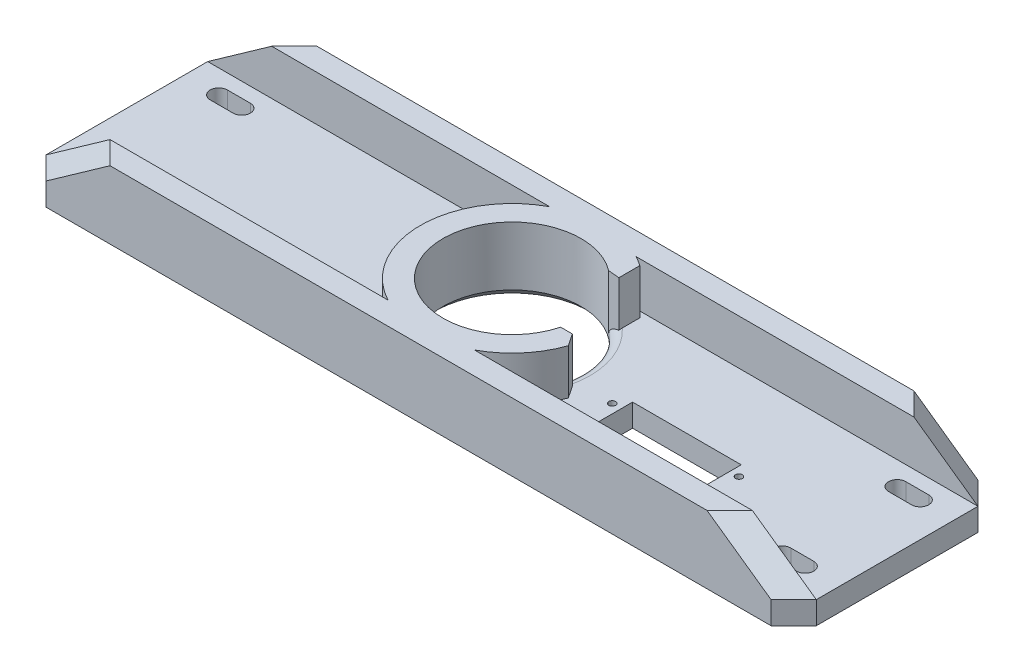
SolidWorks part; units mm, degrees
ref_plane "Front Plane" through (0, 0, 0) normal (0, 0, 1) x (1, 0, 0)
ref_plane "Top Plane" through (0, 0, 0) normal (0, 1, 0) x (1, 0, 0)
ref_plane "Right Plane" through (0, 0, 0) normal (1, 0, 0) x (0, 0, -1)
sketch "Sketch1" plane through (0, 0, 0) normal (0, 1, 0) x (1, 0, 0)
  line L1 (-85.09, 22.86) -> (85.09, 22.86)
  line L2 (-85.09, 22.86) -> (-85.09, -22.86)
  line L3 (-85.09, -22.86) -> (85.09, -22.86)
  line L4 (85.09, 22.86) -> (85.09, -22.86)
  line L5 (-85.09, 22.86) -> (85.09, -22.86) construction
  line L6 (-85.09, -22.86) -> (85.09, 22.86) construction
  point P0 (0, 0)
  dimension "D1" = 170.18
  dimension "D2" = 45.72
extrude "Boss-Extrude1" add sketch "Sketch1" along normal blind 5
sketch "Sketch2" plane through (0, 5, 0) normal (0, 1, 0) x (1, 0, 0)
  line L0 (85.09, 22.86) -> (-85.09, 22.86) construction
  line L1 (85.09, -22.86) -> (85.09, 22.86) construction
  line L2 (-77.4775, 14.6) -> (-72.3975, 14.6)
  line L3 (-77.4775, 10.8) -> (-72.3975, 10.8)
  line L4 (-77.47, -10.8) -> (-72.39, -10.8)
  line L5 (72.39, 14.6) -> (77.47, 14.6)
  line L6 (-72.39, -14.6) -> (-77.47, -14.6)
  line L7 (72.39, -10.8) -> (77.47, -10.8)
  line L8 (77.47, 10.8) -> (72.39, 10.8)
  line L10 (77.47, -14.6) -> (72.39, -14.6)
  arc A0 (-77.4775, 14.6) -> (-77.4775, 10.8) centre (-77.4775, 12.7) ccw
  arc A1 (77.47, 10.8) -> (77.47, 14.6) centre (77.47, 12.7) ccw
  arc A2 (-77.47, -10.8) -> (-77.47, -14.6) centre (-77.47, -12.7) ccw
  arc A3 (77.47, -14.6) -> (77.47, -10.8) centre (77.47, -12.7) ccw
  arc A4 (-72.3975, 10.8) -> (-72.3975, 14.6) centre (-72.3975, 12.7) ccw
  arc A5 (-72.39, -14.6) -> (-72.39, -10.8) centre (-72.39, -12.7) ccw
  arc A6 (72.39, 14.6) -> (72.39, 10.8) centre (72.39, 12.7) ccw
  arc A7 (72.39, -10.8) -> (72.39, -14.6) centre (72.39, -12.7) ccw
  dimension "D2" = 3.8
  dimension "D3" = 3.8
  dimension "D4" = 3.8
  dimension "D5" = 25.4
  dimension "D6" = 25.4
  dimension "D7" = 154.94
  dimension "D8" = 154.9475
  dimension "D9" = 10.16
  dimension "D10" = 10.16
  dimension "D11" = 7.62
  dimension "D12" = 7.62
  dimension "D13" = 3.8
  dimension "D16" = 5.08
  dimension "D17" = 5.08
  dimension "D18" = 5.08
  dimension "D14" = 5.08
extrude "Cut-Extrude1" cut sketch "Sketch2" against normal blind 5
sketch "Sketch4" plane through (0, 5, 0) normal (0, 1, 0) x (1, 0, 0)
  circle A0 centre (0, 0) radius 15.25
  dimension "D1" = 30.5
extrude "Cut-Extrude2" cut sketch "Sketch4" against normal blind 5
sketch "Sketch5" plane through (0, 5, 0) normal (0, 1, 0) x (1, 0, 0)
  line L0 (85.09, -22.86) -> (85.09, 22.86) construction
  line L1 (-85.09, 22.86) -> (85.09, 22.86)
  line L2 (-85.09, 22.86) -> (-85.09, 17.86)
  line L3 (-85.09, 17.86) -> (85.09, 17.86)
  line L4 (85.09, 22.86) -> (85.09, 17.86)
  line L5 (-85.09, 22.86) -> (-85.09, -22.86) construction
  line L6 (85.09, -22.86) -> (-85.09, -22.86)
  line L7 (85.09, -22.86) -> (85.09, -17.86)
  line L8 (85.09, -17.86) -> (-85.09, -17.86)
  line L9 (-85.09, -22.86) -> (-85.09, -17.86)
  dimension "D1" = 5
  dimension "D2" = 5
extrude "Boss-Extrude2" add sketch "Sketch5" along normal blind 10
chamfer "Chamfer1" distance 5 angle 45 4 edges at (85.09, 7.5, 22.86) (85.09, 7.5, -22.86) (-85.09, 7.5, -22.86) (-85.09, 7.5, 22.86)
chamfer "Chamfer2" distance 10 angle 45 4 edges at (82.59, 15, -20.36) (82.59, 15, 20.36) (-82.59, 15, -20.36) (-82.59, 15, 20.36)
sketch "Sketch6" plane through (0, 5, 0) normal (0, 1, 0) x (1, 0, 0)
  circle A0 centre (0, 0) radius 20.25
  circle A1 centre (0, 0) radius 15.25
  dimension "D1" = 5
extrude "Boss-Extrude3" add sketch "Sketch6" along normal blind 10
sketch "Sketch7" plane through (0, 5, 0) normal (0, 1, 0) x (1, 0, 0)
  line L1 (11.6867, 17.86) -> (25.6462, 17.86)
  line L2 (11.6867, 17.86) -> (11.6867, -3.9685)
  line L3 (11.6867, -3.9685) -> (25.6462, -3.9685)
  line L4 (25.6462, 17.86) -> (25.6462, -3.9685)
extrude "Cut-Extrude3" cut sketch "Sketch7" along normal blind 15
sketch "Sketch9" plane through (0, 5, 0) normal (0, 1, 0) x (1, 0, 0)
  line L0 (-65.9479, -22.86) -> (65.9479, -22.86) construction
  line L1 (27, -0.36) -> (51, -0.36)
  line L2 (27, -0.36) -> (27, -12.86)
  line L3 (27, -12.86) -> (51, -12.86)
  line L4 (51, -0.36) -> (51, -12.86)
  line L5 (27, -0.36) -> (51, -12.86) construction
  line L6 (27, -12.86) -> (51, -0.36) construction
  circle A0 centre (0, 0) radius 15.25 construction
  point P0 (39, -6.61)
  dimension "D1" = 24
  dimension "D2" = 12.5
  dimension "D3" = 10
  dimension "D4" = 27
extrude "Cut-Extrude4" cut sketch "Sketch9" against normal blind 5
fillet "Fillet2" radius 2 1 edges at (14.8917, 5, -3.2864)
chamfer "Chamfer3" distance 2 angle 45 1 edges at (0, 0, 15.25)
sketch "Sketch10" plane through (0, 5, 0) normal (0, 1, 0) x (1, 0, 0)
  line L0 (51, -12.86) -> (51, -0.36) construction
  line L1 (27, -12.86) -> (51, -12.86) construction
  line L2 (27, -0.36) -> (27, -12.86) construction
  circle A0 centre (53, -2.86) radius 0.75
  circle A1 centre (53, -10.36) radius 0.75
  circle A2 centre (25, -2.86) radius 0.75
  circle A3 centre (25, -10.36) radius 0.75
  dimension "D1" = 1.5
  dimension "D2" = 1.5
  dimension "D3" = 7.5
  dimension "D4" = 2
  dimension "D5" = 2.5
  dimension "D6" = 1.5
  dimension "D7" = 1.5
  dimension "D8" = 7.5
  dimension "D9" = 2.5
  dimension "D10" = 2
  dimension "D11" = 2
extrude "Cut-Extrude5" cut sketch "Sketch10" against normal blind 5
chamfer "Chamfer4" distance 3 angle 45 1 edges at (19.8573, 10, 3.9685) first distance on face at (15.4797, 10, 11.4927)
chamfer "Chamfer5" distance 3 angle 45 1 edges at (11.6867, 9, -9.7971) first distance on face at (0, 2, 15.25)
